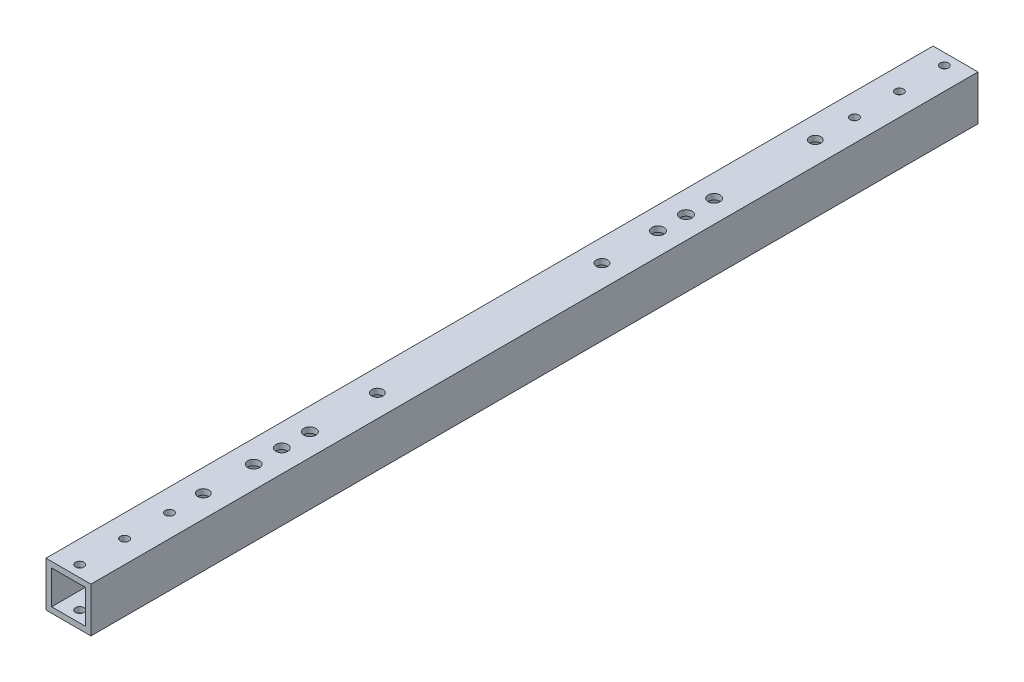
SolidWorks part; units mm, degrees
material "6061-T6 (SS)"
ref_plane "Front Plane" through (0, 0, 0) normal (0, 0, 1) x (1, 0, 0)
ref_plane "Top Plane" through (0, 0, 0) normal (0, 1, 0) x (1, 0, 0)
ref_plane "Right Plane" through (0, 0, 0) normal (1, 0, 0) x (0, 0, -1)
sketch "Sketch1" plane through (0, 0, 0) normal (0, 0, 1) x (1, 0, 0)
  line L1 (-12.7, -12.7) -> (12.7, -12.7)
  line L2 (-12.7, -12.7) -> (-12.7, 12.7)
  line L3 (-12.7, 12.7) -> (12.7, 12.7)
  line L4 (12.7, -12.7) -> (12.7, 12.7)
  line L5 (-12.7, -12.7) -> (12.7, 12.7) construction
  line L6 (-12.7, 12.7) -> (12.7, -12.7) construction
  point P0 (0, 0)
  dimension "D1" = 25.4
  dimension "D2" = 25.4
extrude "Extrude-Thin1" add sketch "Sketch1" along normal blind 501.65 thin thin type one direction reverse wall 3.175
hole_wizard "3/16 (0.1875) Diameter Hole1" positions "3DSketch1" profile "Sketch3" hole size "3/16" standard "ANSI Inch" end condition through all
sketch3d "3DSketch1"
  line L1 (12.7, 12.7, 0) -> (-12.7, 12.7, 0) construction
  line L6 (0, 12.7, 501.65) -> (0, 12.7, 0) construction
  line L7 (12.7, 12.7, 501.65) -> (-12.7, 12.7, 501.65) construction
  point P57 (0, 12.7, 6.35)
  point P59 (0, 12.7, 31.75)
  point P61 (0, 12.7, 57.15)
  point P63 (0, 12.7, 469.9)
  point P65 (0, 12.7, 444.5)
  point P67 (0, 12.7, 495.3)
  dimension "D1" = 25.4
  dimension "D2" = 25.4
  dimension "D3" = 6.35
  dimension "D4" = 25.4
  dimension "D5" = 25.4
  dimension "D6" = 6.35
sketch "Sketch3" plane through (0, 12.7, 495.3) normal (1, 0, 0) x (0, 0, 1)
  line L0 (0, 0) -> (0, 25.4)
  line L1 (0, 25.4) -> (2.3812, 25.4)
  line L2 (2.3812, 25.4) -> (2.3812, 0)
  line L5 (2.3812, 0) -> (0, 0)
  line L11 (0, -6.35) -> (0, 107.95) construction
  dimension "Thru Hole Dia." = 4.7625
  dimension "Thru Hole Depth" = 25.4
hole_wizard "1/4 (0.25) Diameter Hole1" positions "Sketch7" profile "Sketch6" hole size "1/4" standard "ANSI Inch"
sketch "Sketch7" plane through (0, 12.7, 0) normal (0, 1, 0) x (1, 0, 0)
  point P6 (0, -79.3)
  point P9 (0, -425.4029)
  point P23 (0, -326.968)
  point P26 (0, -199.95)
sketch "Sketch6" plane through (0, 12.7, 79.3) normal (1, 0, 0) x (0, 0, 1)
  line L0 (0, 0) -> (0, 27.3077)
  line L1 (0, 27.3077) -> (3.175, 25.4)
  line L2 (3.175, 25.4) -> (3.175, 0)
  line L5 (3.175, 0) -> (0, 0)
  line L10 (0, 27.3077) -> (-3.175, 25.4) construction
  line L11 (0, -6.35) -> (0, 107.95) construction
  dimension "Hole Dia." = 6.35
  dimension "Hole Depth" = 25.4
  dimension "Drill Angle" = 118
hole_wizard "1/4 Clearance Hole1" positions "Sketch8" profile "Sketch9" hole size "1/4" standard "ANSI Inch"
sketch "Sketch8" plane through (381, 12.7, 250.825) normal (0, 1, 0) x (1, 0, 0)
  point P0 (381, 82.55)
  point P3 (381, 98.425)
  point P6 (381, 114.3)
  point P9 (381, -146.05)
  point P12 (381, -130.175)
  point P15 (381, -114.3)
  point P18 (-381, -146.05)
  point P21 (-381, -130.175)
  point P24 (-381, -114.3)
  point P27 (-381, 82.55)
  point P30 (-381, 98.425)
  point P33 (-381, 114.3)
sketch "Sketch9" plane through (762, 12.7, 168.275) normal (1, 0, 0) x (0, 0, 1)
  line L0 (0, 0) -> (0, 40.1298)
  line L1 (0, 40.1298) -> (3.3782, 38.1)
  line L2 (3.3782, 38.1) -> (3.3782, 0)
  line L3 (3.3782, 0) -> (0, 0)
  line L4 (0, 40.1298) -> (-3.3782, 38.1) construction
  line L5 (0, -6.35) -> (0, 107.95) construction
  dimension "Hole Dia." = 6.7564
  dimension "Hole Depth" = 38.1
  dimension "Drill Angle" = 118
